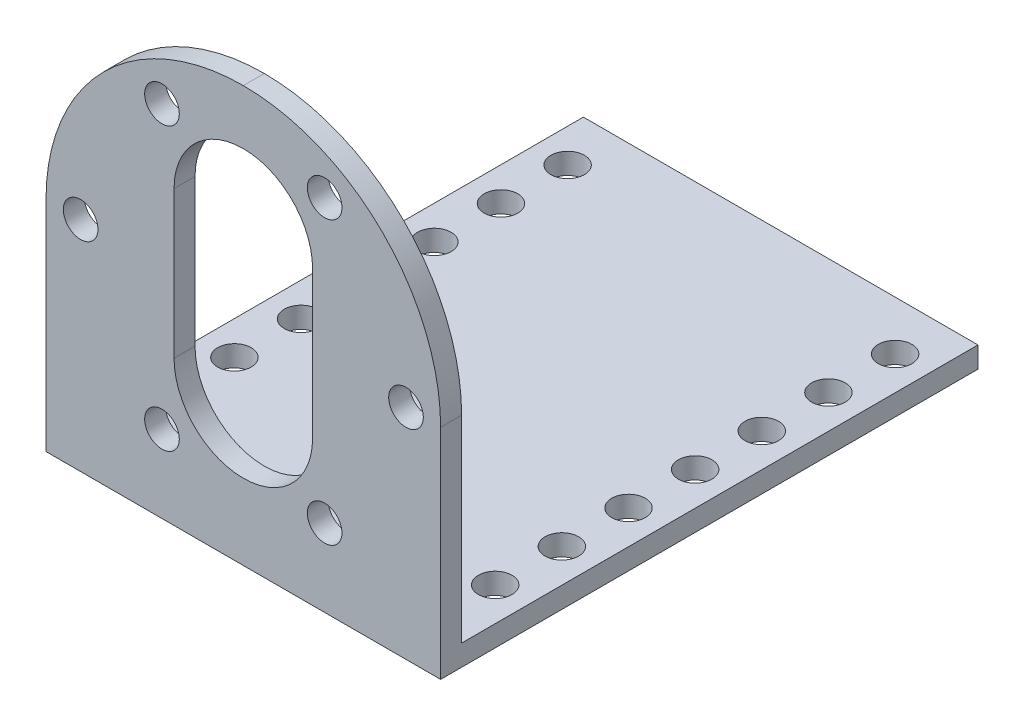
SolidWorks part; units mm, degrees
ref_plane "Front Plane" through (0, 0, 0) normal (0, 0, 1) x (1, 0, 0)
ref_plane "Top Plane" through (0, 0, 0) normal (0, 1, 0) x (1, 0, 0)
ref_plane "Right Plane" through (0, 0, 0) normal (1, 0, 0) x (0, 0, -1)
sketch "Sketch1" plane through (0, 0, 0) normal (0, 1, 0) x (1, 0, 0)
  line L1 (-18.8, -25.6) -> (18.8, -25.6)
  line L2 (-18.8, -25.6) -> (-18.8, 25.6)
  line L3 (-18.8, 25.6) -> (18.8, 25.6)
  line L4 (18.8, -25.6) -> (18.8, 25.6)
  line L5 (-18.8, -25.6) -> (18.8, 25.6) construction
  line L6 (-18.8, 25.6) -> (18.8, -25.6) construction
  point P0 (0, 0)
  dimension "D1" = 37.6
  dimension "D2" = 51.2
extrude "Boss-Extrude1" add sketch "Sketch1" along normal blind 39.6
sketch "Sketch2" plane through (0, 39.6, 0) normal (0, 1, 0) x (1, 0, 0)
  line L0 (18.8, -25.6) -> (18.8, 25.6) construction
  line L1 (-18.8, 25.6) -> (18.8, 25.6)
  line L2 (-18.8, 25.6) -> (-18.8, -23.6)
  line L3 (-18.8, -23.6) -> (18.8, -23.6)
  line L4 (18.8, 25.6) -> (18.8, -23.6)
  line L5 (-18.8, -25.6) -> (18.8, -25.6) construction
  dimension "D1" = 2
extrude "Cut-Extrude1" cut sketch "Sketch2" against normal offset from surface (37.6 mm away) 2 up to face at (0, 0, 0)
fillet "Fillet1" radius 18.8 2 edges at (18.8, 39.6, 24.6) (-18.8, 39.6, 24.6)
sketch "Sketch4" plane through (0, 0, 0) normal (0, -1, 0) x (1, 0, 0)
  line L0 (-15.6, 25.6) -> (-15.6, -25.6) construction
  line L1 (-18.8, 25.6) -> (18.8, 25.6) construction
  line L2 (18.8, -25.6) -> (-18.8, -25.6) construction
  line L3 (15.6, 25.6) -> (15.6, -25.6) construction
  line L5 (-15.6, 0) -> (15.6, 0) construction
  circle A0 centre (-15.6, 17.2) radius 1.6
  circle A1 centre (15.6, 17.2) radius 1.6
  circle A2 centre (-15.6, 10.85) radius 1.6
  circle A3 centre (15.6, 10.85) radius 1.6
  circle A4 centre (-15.6, 4.5) radius 1.6
  circle A5 centre (15.6, 4.5) radius 1.6
  circle A6 centre (-15.6, -1.85) radius 1.6
  circle A7 centre (15.6, -1.85) radius 1.6
  circle A8 centre (-15.6, -8.2) radius 1.6
  circle A9 centre (15.6, -8.2) radius 1.6
  circle A10 centre (-15.6, -14.55) radius 1.6
  circle A11 centre (15.6, -14.55) radius 1.6
  circle A12 centre (-15.6, -20.9) radius 1.6
  circle A13 centre (15.6, -20.9) radius 1.6
  point P10 (0, 0)
  dimension "D2" = 3.2
  dimension "D1" = 31.2
  dimension "D3" = 8.4
  dimension "D4" = 8.4
  dimension "D6" = 4.7
  dimension "D5" = 7
extrude "Cut-Extrude2" cut sketch "Sketch4" against normal through all
sketch "Sketch5" plane through (0, 0, 25.6) normal (0, 0, 1) x (1, 0, 0)
  line L0 (0, 39.6) -> (0, 2) construction
  line L1 (0, 27.8) -> (0, 13.8) construction
  line L2 (6.6, 27.8) -> (6.6, 13.8)
  line L3 (-6.6, 27.8) -> (-6.6, 13.8)
  line L4 (-15.5, 20.8) -> (15.5, 20.8) construction
  line L5 (-7.75, 34.2234) -> (0, 20.8) construction
  line L6 (7.75, 34.2234) -> (0, 20.8) construction
  line L7 (-7.75, 7.3766) -> (0, 20.8) construction
  line L8 (7.75, 7.3766) -> (0, 20.8) construction
  circle A0 centre (0, 20.8) radius 18.8 construction
  arc A1 (6.6, 27.8) -> (-6.6, 27.8) centre (0, 27.8) ccw
  arc A2 (-6.6, 13.8) -> (6.6, 13.8) centre (0, 13.8) ccw
  arc A3 (0, 39.6) -> (-18.8, 20.8) centre (0, 20.8) ccw construction
  circle A4 centre (0, 20.8) radius 15.5 construction
  circle A5 centre (-15.5, 20.8) radius 1.65
  circle A6 centre (15.5, 20.8) radius 1.65
  circle A7 centre (-7.75, 34.2234) radius 1.65
  circle A8 centre (7.75, 34.2234) radius 1.65
  circle A9 centre (7.75, 7.3766) radius 1.65
  circle A10 centre (-7.75, 7.3766) radius 1.65
  point P6 (0, 20.8)
  dimension "D3" = 31
  dimension "D4" = 3.3
  dimension "D1" = 13.2
  dimension "D2" = 14
  dimension "D5" = 60
  dimension "D6" = 60
  dimension "D7" = 60
  dimension "D8" = 60
extrude "Cut-Extrude3" cut sketch "Sketch5" against normal through all
